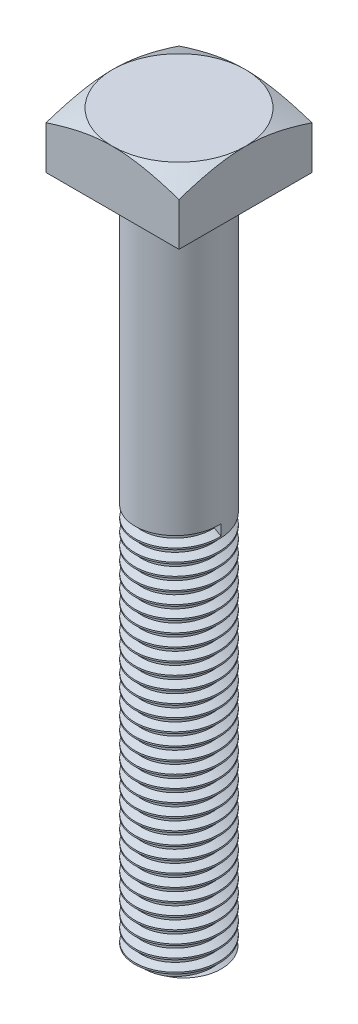
SolidWorks part; units mm, degrees
material "Gray Cast Iron"
ref_plane "Front Plane" through (0, 0, 0) normal (0, 0, 1) x (1, 0, 0)
ref_plane "Top Plane" through (0, 0, 0) normal (0, 1, 0) x (1, 0, 0)
ref_plane "Right Plane" through (0, 0, 0) normal (1, 0, 0) x (0, 0, -1)
sketch "Sketch1" plane through (0, 0, 0) normal (0, 1, 0) x (1, 0, 0)
  line L1 (-9.5, 9.5) -> (9.5, 9.5)
  line L2 (-9.5, 9.5) -> (-9.5, -9.5)
  line L3 (-9.5, -9.5) -> (9.5, -9.5)
  line L4 (9.5, 9.5) -> (9.5, -9.5)
  line L5 (-9.5, 9.5) -> (9.5, -9.5) construction
  line L6 (-9.5, -9.5) -> (9.5, 9.5) construction
  circle A0 centre (0, 0) radius 6
  point P0 (0, 0)
  dimension "D2" = 12
  dimension "D1" = 19
extrude "Boss-Extrude1" add sketch "Sketch1" against normal blind 104 contours A0 region at (0, 0, 0)
extrude "Boss-Extrude2" add sketch "Sketch1<3>" against normal blind 8
sketch "Sketch1<3>" plane through (0, 0, 0) normal (0, 1, 0) x (1, 0, 0) same geometry as "Sketch1"
sketch "Sketch2" plane through (0, 0, 0) normal (1, 0, 0) x (0, 0, -1)
  line L0 (0, 0) -> (0, -50000) construction
  line L1 (9.5, 0) -> (16.3557, 0)
  line L2 (16.3557, 0) -> (16.3557, -3.1969)
  line L3 (16.3557, -3.1969) -> (9.5, 0)
  dimension "D1" = 25
revolve "Cut-Revolve1" cut sketch "Sketch2" angle 360 about L0
thread "Thread1" pitch 1.75 method cut profile "Thread Profile1" start angle 0, offset 2, length 56, pitch 1.75, diameter 12
ref_plane "Plane1" through (6, -106, 0) normal (0, 0, 1) x (1, 0, 0)
sketch "Thread Profile1" plane through (6, -106, 0) normal (0, 0, 1) x (1, 0, 0)
  line L0 (0, 0) -> (0, 1.75) construction
  line L11 (0, 0) -> (0, 1.5312)
  line L12 (0, 1.5312) -> (-0.9472, 0.9844)
  line L13 (-0.9472, 0.9844) -> (-0.9472, 0.5469)
  line L15 (-0.9472, 0.5469) -> (0, 0)
  line L17 (-0.9472, 0.7656) -> (0, 0.7656) construction
  point P2 (0, 0)
  dimension "Pitch" = 1.75
  dimension "Profile_Angle" = 60
  dimension "Profile_Land" = 0.4375
  dimension "Profile_Height" = 0.9472
